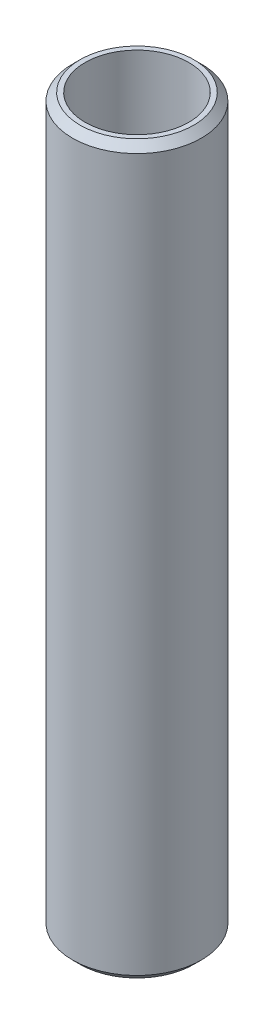
SolidWorks part; units mm, degrees
ref_plane "Front Plane" through (0, 0, 0) normal (0, 0, 1) x (1, 0, 0)
ref_plane "Top Plane" through (0, 0, 0) normal (0, 1, 0) x (1, 0, 0)
ref_plane "Right Plane" through (0, 0, 0) normal (1, 0, 0) x (0, 0, -1)
sketch "Sketch1" plane through (0, 0, 0) normal (0, 1, 0) x (1, 0, 0)
  circle A0 centre (0, 0) radius 27.5
  dimension "SHAFT_OD" = 55
extrude "Boss-Extrude1" add sketch "Sketch1" along normal blind 310.6076
sketch "Sketch2" plane through (0, 0, 0) normal (0, 1, 0) x (1, 0, 0)
  circle A0 centre (0, 0) radius 22.1615
  dimension "BORE_D" = 44.323
extrude "Cut-Extrude1" cut sketch "Sketch2" along normal through all
chamfer "Chamfer1" distance 3.2177 angle 45 2 edges at (0, 310.6076, 27.5) (0, 0, 27.5)
